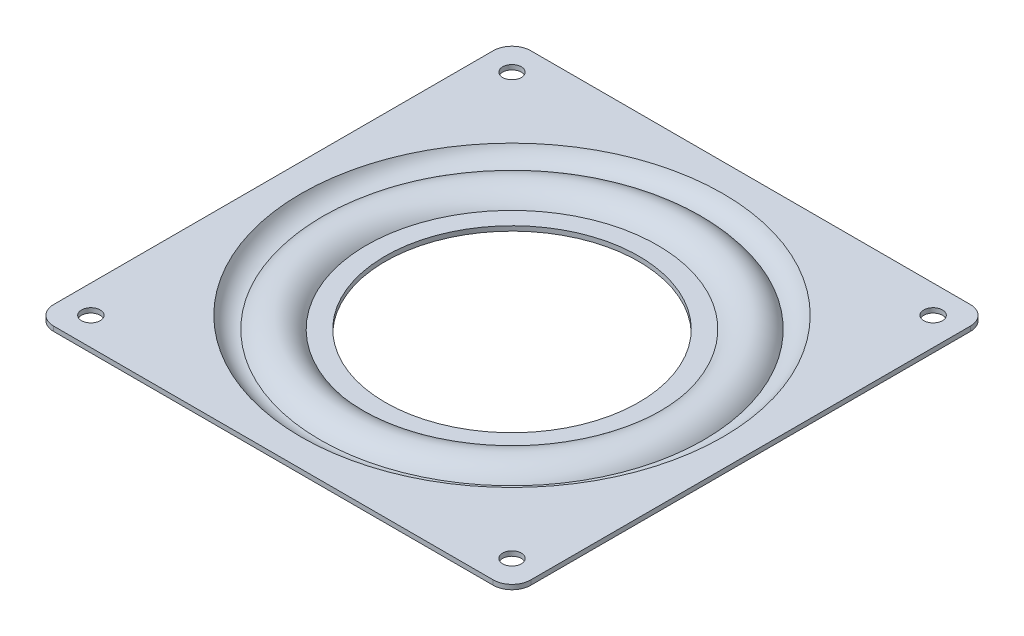
SolidWorks part; units mm, degrees
ref_plane "前视基准面" through (0, 0, 0) normal (0, 0, 1) x (1, 0, 0)
ref_plane "上视基准面" through (0, 0, 0) normal (0, 1, 0) x (1, 0, 0)
ref_plane "右视基准面" through (0, 0, 0) normal (1, 0, 0) x (0, 0, -1)
sketch "草图1" plane through (0, 0, 0) normal (0, 0, 1) x (1, 0, 0)
  line L0 (-36.7805, 0) -> (-35.9228, 0)
  line L1 (0, 6.9172) -> (0, -6.9172) construction
  line L2 (-31, -2.5698) -> (-27, -2.5698)
  line L3 (-35.9228, 0) -> (0, 0) construction
  line L4 (0, 0) -> (43.3864, 0) construction
  line L5 (-43.3864, 0) -> (-36.7805, 0) construction
  line L6 (-31.5531, -3.5698) -> (-27, -3.5698)
  line L7 (-27, -2.5698) -> (-27, -3.5698)
  line L8 (-44.9105, 0) -> (-45.8139, -0.4289)
  arc A0 (-44.9105, 0) -> (-40.8455, -2.5698) centre (-40.8455, 1.9302) ccw
  arc A1 (-40.8455, -2.5698) -> (-31, -2.5698) centre (-35.9228, -6) cw
  arc A2 (-40.8455, -2.5698) -> (-36.8127, -0.0664) centre (-40.8455, 1.9302) ccw construction
  arc A3 (-36.8127, -0.0664) -> (-36.7805, 0) centre (-40.8455, 1.9302) ccw
  arc A4 (-45.8139, -0.4289) -> (-40.2759, -3.5402) centre (-40.8455, 1.9302) ccw
  arc A5 (-40.2759, -3.5402) -> (-31.5531, -3.5698) centre (-35.9228, -6) cw
  point P4 (0, 0)
  point P8 (0, 0)
  dimension "D1" = 4.5
  dimension "D2" = 6
  dimension "D3" = 27
  dimension "D4" = 4
revolve "旋转1" add sketch "草图1" angle 360 about L1 region at (-33.2348, -0.8509, 0)
sketch "草图2" plane through (0, 0, 0) normal (0, 1, 0) x (1, 0, 0)
  line L1 (-46.8, 50.8) -> (46.8, 50.8)
  line L2 (-50.8, 46.8) -> (-50.8, -46.8)
  line L3 (-46.8, -50.8) -> (46.8, -50.8)
  line L4 (50.8, 46.8) -> (50.8, -46.8)
  line L5 (-50.8, 50.8) -> (50.8, -50.8) construction
  line L6 (-50.8, -50.8) -> (50.8, 50.8) construction
  circle A0 centre (0, 0) radius 44.9105 construction
  circle A1 centre (0, 0) radius 44.9105
  arc A2 (-46.8, 50.8) -> (-50.8, 46.8) centre (-46.8, 46.8) ccw
  circle A3 centre (-44.845, 44.845) radius 1.985
  circle A4 centre (44.845, 44.845) radius 1.985
  arc A5 (50.8, 46.8) -> (46.8, 50.8) centre (46.8, 46.8) ccw
  circle A6 centre (44.845, -44.845) radius 1.985
  arc A7 (46.8, -50.8) -> (50.8, -46.8) centre (46.8, -46.8) ccw
  circle A8 centre (-44.845, -44.845) radius 1.985
  arc A9 (-50.8, -46.8) -> (-46.8, -50.8) centre (-46.8, -46.8) ccw
  point P14 (0, 0)
  point P32 (0, 0)
  dimension "D3" = 4
  dimension "D4" = 3.97
  dimension "D5" = 4
  dimension "D1" = 90
  dimension "D2" = 101.6
  dimension "D6" = 63.4204
extrude "凸台-拉伸1" add sketch "草图2" against normal blind 1 contours L2 L3 L4 L1 A2 A3 A1 region at (0, 0, -49.3632)
